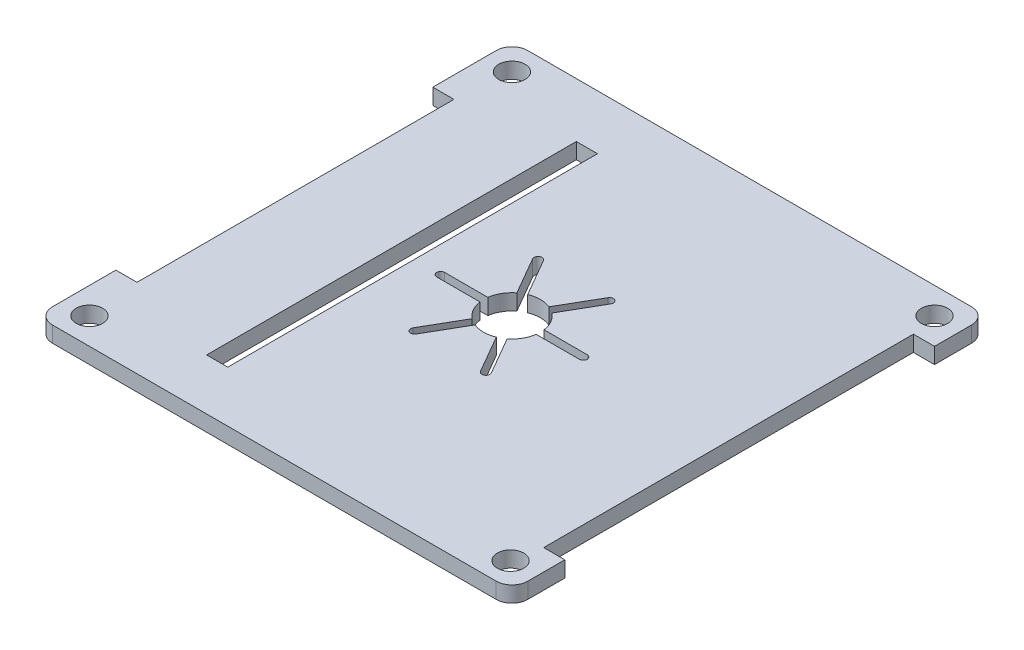
SolidWorks part; units mm, degrees
ref_plane "Front Plane" through (0, 0, 0) normal (0, 0, 1) x (1, 0, 0)
ref_plane "Top Plane" through (0, 0, 0) normal (0, 1, 0) x (1, 0, 0)
ref_plane "Right Plane" through (0, 0, 0) normal (1, 0, 0) x (0, 0, -1)
sketch "Sketch1" plane through (0, 0, 0) normal (0, 1, 0) x (1, 0, 0)
  line L0 (-50.7713, 34.2125) -> (-46.7713, 34.2125)
  line L1 (-50.7713, -40.7875) -> (39.2287, -40.7875)
  line L2 (-50.7713, -40.7875) -> (-50.7713, 49.2125)
  line L3 (-50.7713, 49.2125) -> (39.2287, 49.2125)
  line L4 (39.2287, -40.7875) -> (39.2287, 49.2125)
  line L5 (39.2287, 39.2125) -> (39.2287, -30.7875)
  line L6 (-24.2713, -31.1062) -> (-28.2713, -31.1062)
  line L7 (-46.7713, 34.2125) -> (-46.7713, -25.7875)
  line L8 (-46.7713, -25.7875) -> (-50.7713, -25.7875)
  line L9 (39.2287, 39.2125) -> (35.2287, 39.2125)
  line L10 (35.2287, 39.2125) -> (35.2287, -30.7875)
  line L11 (35.2287, -30.7875) -> (39.2287, -30.7875)
  line L12 (-24.2713, -31.1062) -> (-24.2713, 38.8938)
  line L13 (-24.2713, 38.8938) -> (-28.2713, 38.8938)
  line L14 (-28.2713, -31.1062) -> (-28.2713, 38.8938)
  line L17 (-50.7713, 34.2125) -> (-50.7713, -25.7875)
  point P0 (0, 0)
  point P13 (3.7124, 4.3448)
  dimension "D1" = 90
  dimension "D2" = 90
  dimension "D3" = 15
  dimension "D4" = 15
  dimension "D5" = 4
  dimension "D6" = 4
  dimension "D7" = 18.5
  dimension "D8" = 4
  dimension "D9" = 70
  dimension "D11" = 10
  dimension "D12" = 10
  dimension "D13" = 70
extrude "Boss-Extrude1" add sketch "Sketch1" along normal blind 3 contours L11 L10 L9 L4 L3 L2 L0 L7 L8 L1 L6 L14 L13 L12 | L10 L11 L4 L9 | L8 L7 L0 L2 | L14 L6 L12 L13 region at (-5.2206, 0, -4.2248) region at (-48.7713, 0, -4.2125) region at (37.2287, 0, -4.2125) region at (-26.2713, 0, -3.8938)
extrude "Boss-Extrude2" add sketch "Sketch1<3>" along normal blind 70 contours L8 L7 L0 L2 | L10 L11 L5 L9 region at (-48.7713, 0, -4.2125)
sketch "Sketch1<3>" plane through (0, 0, 0) normal (0, 1, 0) x (1, 0, 0) same geometry as "Sketch1"
extrude "Boss-Extrude3" add sketch "Sketch1<4>" along normal blind 70 contours L14 L13 L12 L6
sketch "Sketch1<4>" plane through (0, 0, 0) normal (0, 1, 0) x (1, 0, 0) same geometry as "Sketch1"
sketch "Sketch5" plane through (-50.7713, 0, 0) normal (-1, 0, 0) x (0, 0, 1)
  line L0 (-8.0225, 70) -> (-8.0225, 0) construction
  line L5 (-34.2125, 70) -> (-34.2125, 3) construction
  circle A0 centre (-8.0225, 60) radius 4
  dimension "D1" = 60
  dimension "D3" = 8
  dimension "D2" = 26.19
extrude "Cut-Extrude4" cut sketch "Sketch5" against normal blind 10
sketch "Sketch6" plane through (0, 3, 0) normal (0, 1, 0) x (1, 0, 0)
  line L0 (-50.7876, 44.2125) -> (49.2124, 44.2125) construction
  line L3 (-50.7876, -35.7875) -> (49.2124, -35.7875) construction
  line L8 (-50.7713, -40.7875) -> (39.2287, -40.7875) construction
  line L9 (-50.7713, 49.2125) -> (39.2287, 49.2125) construction
  circle A0 centre (-45.7876, -35.7875) radius 2.5
  circle A1 centre (-45.7876, 44.2125) radius 2.5
  circle A2 centre (43.7185, 44.2125) radius 2.5
  circle A3 centre (43.7185, -35.7875) radius 2.5
  dimension "D1" = 5
  dimension "D2" = 5
  dimension "D3" = 5
  dimension "D4" = 5
extrude "Cut-Extrude5" cut sketch "Sketch6" against normal blind 10
extrude "Boss-Extrude4" add sketch "Sketch1<5>" along normal blind 80 contours L7 L8 L17 L0
sketch "Sketch1<5>" plane through (0, 0, 0) normal (0, 1, 0) x (1, 0, 0) same geometry as "Sketch1"
extrude "Cut-Extrude6" cut sketch "Sketch5<2>" against normal blind 10
sketch "Sketch5<2>" plane through (-50.7713, 0, 0) normal (-1, 0, 0) x (0, 0, 1) same geometry as "Sketch5"
fillet "Fillet1" radius 3 4 edges at (-50.7713, 1.5, -49.2125) (-50.7713, 1.5, 40.7875) (39.2287, 1.5, -49.2125) (39.2287, 1.5, 40.7875)
fillet "Fillet2" radius 5 4 edges at (-48.7713, 80, -34.2125) (37.2287, 70, -39.2125) (37.2287, 70, 30.7875) (-48.7713, 80, 25.7875)
fillet "Fillet3" radius 4 2 edges at (-26.2713, 70, -38.8938) (-26.2713, 70, 31.1062)
sketch "Sketch7" plane through (39.2287, 0, 0) normal (1, 0, 0) x (0, 0, -1)
  line L0 (-30.7875, -10) -> (39.2125, -10) construction
  line L1 (-30.7875, 65) -> (-30.7875, 3) construction
  line L2 (39.2125, 65) -> (39.2125, 3) construction
  line L3 (-37.7875, 0) -> (46.2125, 0) construction
  circle A0 centre (27.4823, -10) radius 2.5
  dimension "D1" = 10
extrude "Cut-Extrude7" cut sketch "Sketch7" against normal blind 10 rebuild error yes
sketch "Sketch8" plane through (39.2287, 0, 0) normal (1, 0, 0) x (0, 0, -1)
  line L0 (39.2125, 20) -> (-30.7875, 20) construction
  line L1 (39.2125, 65) -> (39.2125, 3) construction
  line L2 (-30.7875, 65) -> (-30.7875, 3) construction
  line L3 (26.9146, 20) -> (8.0207, 38.8939) construction
  circle A0 centre (8.0207, 38.8939) radius 2.5
  dimension "D3" = 5
  dimension "D1" = 26.72
  dimension "D2" = 45
extrude "Cut-Extrude8" cut sketch "Sketch8" against normal blind 10
sketch "Sketch9" plane through (39.2287, 0, 0) normal (1, 0, 0) x (0, 0, -1)
  circle A0 centre (8.0207, 38.8939) radius 3.5
  dimension "D1" = 7
extrude "Cut-Extrude9" cut sketch "Sketch9" against normal up to surface (67.5 mm away) up to face at (-28.2713, 46.6095, -3.8938)
sketch "Sketch26" plane through (0, 3, 0) normal (0, 1, 0) x (1, 0, 0)
  line L0 (39.2287, 39.2125) -> (39.2287, 46.2125) construction
  line L1 (39.2287, -37.7875) -> (39.2287, -30.7875) construction
  circle A0 centre (34.2287, 44.2125) radius 2.5
  circle A2 centre (34.2287, -36.0634) radius 2.5
  dimension "D1" = 5
  dimension "D2" = 5
  dimension "D3" = 5
  dimension "D4" = 5
extrude "Cut-Extrude11" cut sketch "Sketch26" against normal blind 10 contours A2 | A0 region at (34.2287, 3, 36.0634)
sketch "Sketch27" plane through (0, 3, 0) normal (0, 1, 0) x (1, 0, 0)
  line L0 (-49.8926, 48.3339) -> (38.35, -39.9088) construction
  line L1 (38.35, 48.3339) -> (-49.8926, -39.9088) construction
  line L2 (7.7287, 4.2125) -> (-19.2713, 4.2125) construction
  line L3 (7.7287, 3.4625) -> (-19.2713, 3.4625)
  line L4 (7.7287, 4.9625) -> (-19.2713, 4.9625)
  line L5 (0.9787, -7.4788) -> (-12.5213, 15.9039) construction
  line L6 (0.3292, -7.8538) -> (-13.1708, 15.5289)
  line L7 (1.6282, -7.1038) -> (-11.8718, 16.2789)
  line L8 (-12.5213, -7.4788) -> (0.9787, 15.9039) construction
  line L9 (-13.1708, -7.1038) -> (0.3292, 16.2789)
  line L10 (-11.8718, -7.8538) -> (1.6282, 15.5289)
  line L11 (-19.2713, 4.2125) -> (7.7287, 4.2125) construction
  line L12 (-19.2713, 4.9625) -> (7.7287, 4.9625)
  line L13 (-19.2713, 3.4625) -> (7.7287, 3.4625)
  line L14 (-12.5213, 15.9039) -> (0.9787, -7.4788) construction
  line L15 (-11.8718, 16.2789) -> (1.6282, -7.1038)
  line L16 (-13.1708, 15.5289) -> (0.3292, -7.8538)
  line L17 (0.9787, 15.9039) -> (-12.5213, -7.4788) construction
  line L18 (1.6282, 15.5289) -> (-11.8718, -7.8538)
  line L19 (0.3292, 16.2789) -> (-13.1708, -7.1038)
  arc A0 (-47.7713, 49.2125) -> (-50.7713, 46.2125) centre (-47.7713, 46.2125) ccw construction
  arc A1 (36.2287, -40.7875) -> (39.2287, -37.7875) centre (36.2287, -37.7875) ccw construction
  arc A2 (39.2287, 46.2125) -> (36.2287, 49.2125) centre (36.2287, 46.2125) ccw construction
  arc A3 (-50.7713, -37.7875) -> (-47.7713, -40.7875) centre (-47.7713, -37.7875) ccw construction
  arc A4 (7.7287, 3.4625) -> (7.7287, 4.9625) centre (7.7287, 4.2125) ccw
  arc A5 (-19.2713, 4.9625) -> (-19.2713, 3.4625) centre (-19.2713, 4.2125) ccw
  circle A9 centre (-5.7713, 4.2125) radius 5.375
  arc A10 (0.3292, -7.8538) -> (1.6282, -7.1038) centre (0.9787, -7.4788) ccw
  arc A11 (-11.8718, 16.2789) -> (-13.1708, 15.5289) centre (-12.5213, 15.9039) ccw
  arc A12 (-13.1708, -7.1038) -> (-11.8718, -7.8538) centre (-12.5213, -7.4788) ccw
  arc A13 (1.6282, 15.5289) -> (0.3292, 16.2789) centre (0.9787, 15.9039) ccw
  arc A14 (-19.2713, 4.9625) -> (-19.2713, 3.4625) centre (-19.2713, 4.2125) ccw
  arc A15 (7.7287, 3.4625) -> (7.7287, 4.9625) centre (7.7287, 4.2125) ccw
  arc A16 (-11.8718, 16.2789) -> (-13.1708, 15.5289) centre (-12.5213, 15.9039) ccw
  arc A17 (0.3292, -7.8538) -> (1.6282, -7.1038) centre (0.9787, -7.4788) ccw
  arc A18 (1.6282, 15.5289) -> (0.3292, 16.2789) centre (0.9787, 15.9039) ccw
  arc A19 (-13.1708, -7.1038) -> (-11.8718, -7.8538) centre (-12.5213, -7.4788) ccw
  circle A20 centre (-5.7713, 4.2125) radius 2.75
  point P18 (-5.7713, 4.2125)
  point P30 (-5.7713, 4.2125)
  point P37 (-5.7713, 4.2125)
  point P44 (-5.7713, 4.2125)
  point P51 (-5.7713, 4.2125)
  point P58 (-5.7713, 4.2125)
  point P63 (-5.7713, 4.2125)
  dimension "D1" = 10.75
  dimension "D2" = 0.75
  dimension "D3" = 13.5
  dimension "D4" = 6
extrude "Cut-Extrude14" cut sketch "Sketch27" against normal blind 10 contours L3 A5 L4 A4 | L6 A11 L7 A10 | L10 A13 L9 A12
extrude "Cut-Extrude15" cut sketch "Sketch27<7>" against normal blind 10 contours L3 A20 L9 | L6 A20 L4 | L9 A20 L7 | L4 A20 L10 | L7 A20 L3 | L10 A20 L6 region at (-3.7669, 3, -3.0553) region at (-3.7669, 3, -5.3698) region at (-5.7713, 3, -1.898) region at (-5.7713, 3, -6.5271) region at (-7.7757, 3, -3.0553) region at (-7.7757, 3, -5.3698)
sketch "Sketch27<7>" plane through (0, 3, 0) normal (0, 1, 0) x (1, 0, 0) same geometry as "Sketch27"
sketch "Sketch28" plane through (-50.7713, 0, 0) normal (-1, 0, 0) x (0, 0, 1)
  line L0 (-23.4588, 51.635) -> (-8.5312, 68.47)
  line L1 (-8.5312, 68.47) -> (0.4475, 60.5086)
  line L2 (0.4475, 60.5086) -> (-14.4801, 43.6736)
  line L3 (-14.4801, 43.6736) -> (-23.4588, 51.635)
  line L4 (-8.0225, 60) -> (-12.6884, 54.7379) construction
  line L5 (-12.6884, 54.7379) -> (-25.2505, 40.5707) construction
  line L6 (-8.0225, 60) -> (2.1094, 71.4266) construction
  circle A0 centre (-8.0225, 60) radius 4 construction
  circle A1 centre (-8.0225, 60) radius 4
  circle A2 centre (-2.3169, 66.4347) radius 1
  circle A3 centre (-20.6944, 45.709) radius 1
  point P8 (-18.9694, 47.6543)
  dimension "D3" = 2
  dimension "D4" = 8.6
  dimension "D5" = 27.7
  dimension "D1" = 22.5
  dimension "D2" = 12
  dimension "D6" = 2.6
extrude "Cut-Extrude16" cut sketch "Sketch28" against normal up to surface (4 mm away) up to face at (-46.7713, 60, -12.0225)
sketch "Sketch29" plane through (39.2287, 0, 0) normal (1, 0, 0) x (0, 0, -1)
  line L8 (8.0207, 38.8939) -> (0.0593, 47.8726) construction
  line L9 (0.0593, 47.8726) -> (37.8759, 5.2239) construction
  line L10 (8.5294, 47.3639) -> (23.457, 30.5289)
  line L11 (23.457, 30.5289) -> (14.4783, 22.5675)
  line L12 (14.4783, 22.5675) -> (-0.4493, 39.4025)
  line L13 (-0.4493, 39.4025) -> (8.5294, 47.3639)
  circle A6 centre (8.0207, 38.8939) radius 3.5 construction
  circle A7 centre (8.0207, 38.8939) radius 3.5
  circle A8 centre (2.3151, 45.3286) radius 1
  circle A9 centre (20.6926, 24.6028) radius 1
  point P4 (4.04, 43.3832)
  point P28 (18.9676, 26.5482)
  dimension "D4" = 2.6
  dimension "D5" = 27.7
  dimension "D6" = 2
  dimension "D7" = 2
  dimension "D2" = 12
  dimension "D3" = 22.5
  dimension "D8" = 8.6
extrude "Cut-Extrude18" cut sketch "Sketch29" against normal up to surface (4 mm away) up to face at (35.2287, 38.8939, -11.5207)
sketch "Sketch31" plane through (0, 3, 0) normal (0, 1, 0) x (1, 0, 0)
  circle A0 centre (-5.7713, 4.2125) radius 5.375
  dimension "D1" = 10.75
extrude "Cut-Extrude19" cut sketch "Sketch31" against normal blind 10
sketch "Sketch32" plane through (39.2287, 0, 0) normal (1, 0, 0) x (0, 0, -1)
  line L1 (-31.1062, 3) -> (40.5355, 3)
  line L2 (-31.1062, 3) -> (-31.1062, 82.5175)
  line L3 (-31.1062, 82.5175) -> (40.5355, 82.5175)
  line L4 (40.5355, 3) -> (40.5355, 82.5175)
extrude "Cut-Extrude20" cut sketch "Sketch32" against normal through all
sketch "Sketch33" plane through (0, 3, 0) normal (0, 1, 0) x (1, 0, 0)
  line L4 (39.2287, -30.7875) -> (39.2287, 39.2125)
  line L5 (35.2287, -30.7875) -> (39.2287, -30.7875)
  line L6 (35.2287, 39.2125) -> (35.2287, -30.7875)
  line L7 (39.2287, 39.2125) -> (35.2287, 39.2125)
  line L8 (39.2287, -30.7875) -> (39.2287, 39.2125)
  line L9 (35.2287, -30.7875) -> (39.2287, -30.7875)
  line L10 (35.2287, 39.2125) -> (35.2287, -30.7875)
  line L11 (39.2287, 39.2125) -> (35.2287, 39.2125)
  line L12 (-50.7713, -40.7875) -> (39.2287, -40.7875)
  line L13 (39.2287, -40.7875) -> (39.2287, 49.2125)
  line L14 (39.2287, 49.2125) -> (-50.7713, 49.2125)
  line L15 (-50.7713, 49.2125) -> (-50.7713, -40.7875)
  line L16 (-50.7713, -40.7875) -> (39.2287, -40.7875)
  line L17 (39.2287, -40.7875) -> (39.2287, 49.2125)
  line L18 (39.2287, 49.2125) -> (-50.7713, 49.2125)
  line L19 (-50.7713, 49.2125) -> (-50.7713, -40.7875)
  line L20 (-46.7713, 34.2125) -> (-50.7713, 34.2125)
  line L21 (-46.7713, -25.7875) -> (-46.7713, 34.2125)
  line L22 (-50.7713, -25.7875) -> (-46.7713, -25.7875)
  line L23 (-50.7713, 34.2125) -> (-50.7713, -25.7875)
  line L24 (-46.7713, 34.2125) -> (-50.7713, 34.2125)
  line L25 (-46.7713, -25.7875) -> (-46.7713, 34.2125)
  line L26 (-50.7713, -25.7875) -> (-46.7713, -25.7875)
  line L27 (-50.7713, 34.2125) -> (-50.7713, -25.7875)
  line L28 (-28.2713, -31.1062) -> (-24.2713, -31.1062)
  line L29 (-28.2713, 38.8938) -> (-28.2713, -31.1062)
  line L30 (-24.2713, 38.8938) -> (-28.2713, 38.8938)
  line L31 (-24.2713, -31.1062) -> (-24.2713, 38.8938)
  line L32 (-28.2713, -31.1062) -> (-24.2713, -31.1062)
  line L33 (-28.2713, 38.8938) -> (-28.2713, -31.1062)
  line L34 (-24.2713, 38.8938) -> (-28.2713, 38.8938)
  line L35 (-24.2713, -31.1062) -> (-24.2713, 38.8938)
  line M18 (39.2287, -37.7875) -> (39.2287, 46.2125)
  dimension "D1" = 0
  dimension "D2" = 0
  dimension "D3" = 0
  dimension "D4" = 0
extrude "Cut-Extrude21" cut sketch "Sketch33" against normal through all contours L32 L35 L34 L33 | L19 L26 L25 L24 | L11 L10 L9 M18 region at (37.2287, 3, -4.2125) region at (-48.7713, 3, -4.2125) region at (-26.2713, 3, -3.8938)
